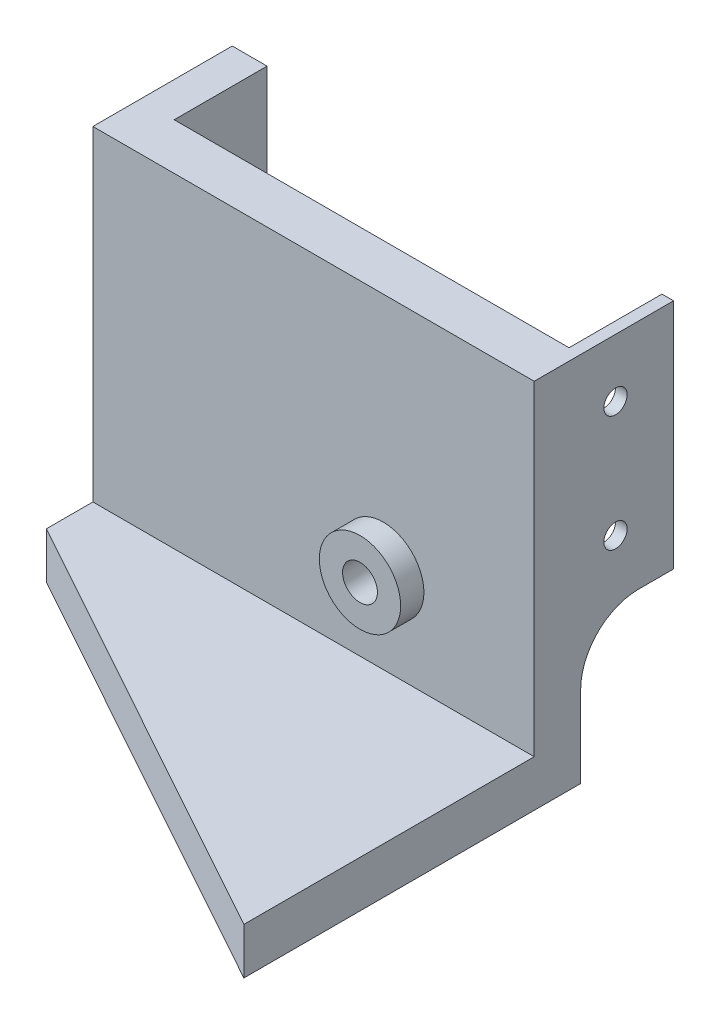
SolidWorks part; units mm, degrees
ref_plane "Front Plane" through (0, 0, 0) normal (0, 0, 1) x (1, 0, 0)
ref_plane "Top Plane" through (0, 0, 0) normal (0, 1, 0) x (1, 0, 0)
ref_plane "Right Plane" through (0, 0, 0) normal (1, 0, 0) x (0, 0, -1)
sketch "Sketch1" plane through (0, 0, 0) normal (0, 1, 0) x (1, 0, 0)
  line L1 (0, 0) -> (38, 0)
  line L2 (0, 0) -> (0, 12)
  line L3 (0, 12) -> (38, 12)
  line L4 (38, 0) -> (38, 12)
  line L5 (3, 12) -> (37, 12)
  line L6 (3, 12) -> (3, 4)
  line L7 (3, 4) -> (37, 4)
  line L8 (37, 12) -> (37, 4)
  dimension "D1" = 12
  dimension "D2" = 38
  dimension "D3" = 34
  dimension "D4" = 3
  dimension "D5" = 3
  dimension "10" = 8
extrude "Boss-Extrude1" add sketch "Sketch1" along normal blind 20 contours L3 L8 L7 L6 L2 L1 L4 region at (17.5217, 0, -3.0435)
sketch "Sketch2" plane through (0, 0, 0) normal (0, -1, 0) x (1, 0, 0)
  line L0 (38, 0) -> (38, -12) construction
  line L1 (0, 0) -> (38, 0)
  line L2 (0, 0) -> (0, -4)
  line L3 (0, -4) -> (38, -4)
  line L4 (38, 0) -> (38, -4)
extrude "Boss-Extrude2" add sketch "Sketch2" along normal blind 12
fillet "Fillet1" radius 5 2 edges at (1.5, 0, -4) (37.5, 0, -4)
sketch "Sketch3" plane through (0, 0, 0) normal (0, 0, 1) x (1, 0, 0)
  line L0 (38, 20) -> (38, -12) construction
  line L1 (0, -12) -> (38, -12)
  line L2 (0, -12) -> (0, -8)
  line L3 (0, -8) -> (38, -8)
  line L4 (38, -12) -> (38, -8)
  dimension "D1" = 4
extrude "Boss-Extrude3" add sketch "Sketch3" along normal blind 25 contours L3 L4 L1 L2
sketch "Sketch4" plane through (0, 0, 0) normal (0, 0, 1) x (1, 0, 0)
  line L0 (0, -8) -> (38, -8) construction
  line L1 (0, 20) -> (0, -8) construction
  circle A0 centre (25, -0.5) radius 1.5
  circle A1 centre (25, -0.5) radius 3.5
  point P6 (0, 0)
  dimension "D1" = 3
  dimension "D2" = 7.5
  dimension "D4" = 25
  dimension "D3" = 2
extrude "Boss-Extrude4" add sketch "Sketch4" along normal blind 2
sketch "Sketch5" plane through (0, 0, 2) normal (0, 0, 1) x (1, 0, 0)
  circle A0 centre (25, -0.5) radius 1.5 construction
  circle A1 centre (25, -0.5) radius 1.5
extrude "Cut-Extrude1" cut sketch "Sketch5" against normal through all contours A1
sketch "Sketch6" plane through (0, -8, 0) normal (0, 1, 0) x (1, 0, 0)
  line L0 (38, -25) -> (0, -4)
  line L3 (0, -25) -> (0, 0) construction
  line L4 (0, -4) -> (0, -25)
  line L5 (0, -25) -> (38, -25)
  dimension "D1" = 4
extrude "Cut-Extrude2" cut sketch "Sketch6" against normal blind 10
sketch "Sketch8" plane through (38, 0, 0) normal (1, 0, 0) x (0, 0, -1)
  circle A0 centre (7, 15) radius 1
  circle A1 centre (7, 5) radius 1
  dimension "D2" = 2
  dimension "D1" = 10
extrude "Cut-Extrude3" cut sketch "Sketch8" against normal through all both and the other way through all
